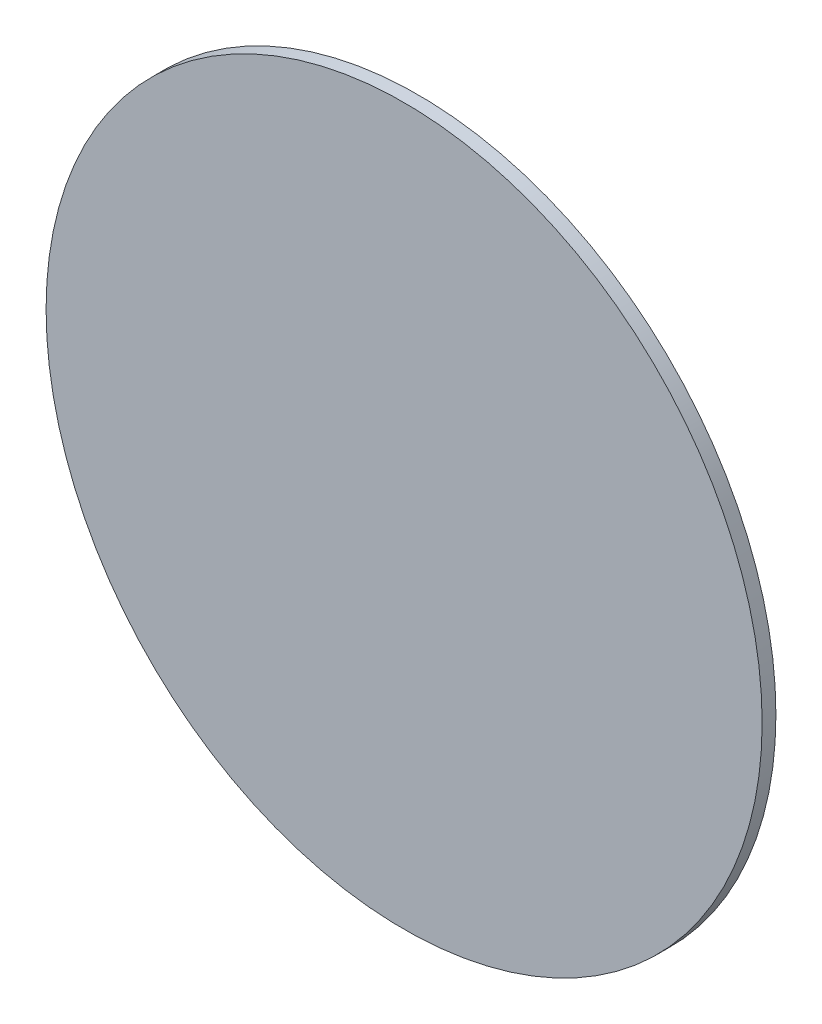
SolidWorks part; units mm, degrees
material "6061 Alloy"
ref_plane "Front Plane" through (0, 0, 0) normal (0, 0, 1) x (1, 0, 0)
ref_plane "Top Plane" through (0, 0, 0) normal (0, 1, 0) x (1, 0, 0)
ref_plane "Right Plane" through (0, 0, 0) normal (1, 0, 0) x (0, 0, -1)
sketch "Sketch1" plane through (0, 0, 0) normal (0, 0, 1) x (1, 0, 0)
  line L0 (6.5991, -21.59) -> (27.0559, -57.0222) construction
  line L1 (20.4568, -68.4522) -> (-20.4568, -68.4522) construction
  line L2 (-27.0559, -57.0222) -> (-6.5991, -21.59) construction
  line L3 (-15.3979, -16.51) -> (-35.8547, -51.9422) construction
  line L4 (-49.0529, -51.9422) -> (-69.5097, -16.51) construction
  line L5 (-62.9106, -5.08) -> (-21.997, -5.08) construction
  line L6 (-21.997, 5.08) -> (-62.9106, 5.08) construction
  line L7 (-69.5097, 16.51) -> (-49.0529, 51.9422) construction
  line L8 (-35.8547, 51.9422) -> (-15.3979, 16.51) construction
  line L9 (-6.5991, 21.59) -> (-27.0559, 57.0222) construction
  line L10 (-20.4568, 68.4522) -> (20.4568, 68.4522) construction
  line L11 (27.0559, 57.0222) -> (6.5991, 21.59) construction
  line L12 (15.3979, 16.51) -> (35.8547, 51.9422) construction
  line L13 (49.0529, 51.9422) -> (69.5097, 16.51) construction
  line L14 (62.9106, 5.08) -> (21.997, 5.08) construction
  line L15 (21.997, -5.08) -> (62.9106, -5.08) construction
  line L16 (69.5097, -16.51) -> (49.0529, -51.9422) construction
  line L17 (35.8547, -51.9422) -> (15.3979, -16.51) construction
  circle A0 centre (0, 114.3) radius 34.8615 construction
  circle A1 centre (98.9867, 57.15) radius 34.8615 construction
  circle A2 centre (98.9867, -57.15) radius 34.8615 construction
  circle A3 centre (0, -114.3) radius 34.8615 construction
  circle A4 centre (-98.9867, -57.15) radius 34.8615 construction
  circle A5 centre (-98.9867, 57.15) radius 34.8615 construction
  circle A6 centre (0, 0) radius 165.1
  circle A7 centre (0, 0) radius 12.7 construction
  arc A8 (-20.4568, -68.4522) -> (-27.0559, -57.0222) centre (-20.4568, -60.8322) cw construction
  arc A9 (27.0559, -57.0222) -> (20.4568, -68.4522) centre (20.4568, -60.8322) cw construction
  arc A10 (6.5991, -21.59) -> (-6.5991, -21.59) centre (0, -25.4) ccw construction
  arc A11 (-69.5097, -16.51) -> (-62.9106, -5.08) centre (-62.9106, -12.7) cw construction
  arc A12 (-35.8547, -51.9422) -> (-49.0529, -51.9422) centre (-42.4538, -48.1322) cw construction
  arc A13 (-15.3979, -16.51) -> (-21.997, -5.08) centre (-21.997, -12.7) ccw construction
  arc A14 (-49.0529, 51.9422) -> (-35.8547, 51.9422) centre (-42.4538, 48.1322) cw construction
  arc A15 (-62.9106, 5.08) -> (-69.5097, 16.51) centre (-62.9106, 12.7) cw construction
  arc A16 (-21.997, 5.08) -> (-15.3979, 16.51) centre (-21.997, 12.7) ccw construction
  arc A17 (20.4568, 68.4522) -> (27.0559, 57.0222) centre (20.4568, 60.8322) cw construction
  arc A18 (-27.0559, 57.0222) -> (-20.4568, 68.4522) centre (-20.4568, 60.8322) cw construction
  arc A19 (-6.5991, 21.59) -> (6.5991, 21.59) centre (0, 25.4) ccw construction
  arc A20 (69.5097, 16.51) -> (62.9106, 5.08) centre (62.9106, 12.7) cw construction
  arc A21 (35.8547, 51.9422) -> (49.0529, 51.9422) centre (42.4538, 48.1322) cw construction
  arc A22 (15.3979, 16.51) -> (21.997, 5.08) centre (21.997, 12.7) ccw construction
  arc A23 (49.0529, -51.9422) -> (35.8547, -51.9422) centre (42.4538, -48.1322) cw construction
  arc A24 (62.9106, -5.08) -> (69.5097, -16.51) centre (62.9106, -12.7) cw construction
  arc A25 (21.997, -5.08) -> (15.3979, -16.51) centre (21.997, -12.7) ccw construction
  point P16 (0, 0)
  point P22 (-33.655, -68.4522)
  point P27 (0, -10.16)
  point P76 (0, 0)
  dimension "D1" = 69.723
  dimension "D4" = 330.2
  dimension "D5" = 25.4
  dimension "D6" = 67.31
  dimension "D7" = 7.62
  dimension "D10" = 114.3
  dimension "D2" = 114.3
  dimension "D8" = 25.4
  dimension "D3" = 6
  dimension "D9" = 6
extrude "Boss-Extrude1" add sketch "Sketch1" along normal mid plane 6.35
sketch "Sketch2" plane through (0, 0, -3.175) normal (0, 0, -1) x (-1, 0, 0)
  line L1 (-21.997, 5.08) -> (-62.9106, 5.08) construction
  circle A0 centre (-23.8125, 0) radius 2.5908 construction
  circle A2 centre (-11.9062, 20.6222) radius 2.5908 construction
  circle A3 centre (11.9063, 20.6222) radius 2.5908 construction
  circle A4 centre (23.8125, 0) radius 2.5908 construction
  circle A5 centre (11.9062, -20.6222) radius 2.5908 construction
  circle A6 centre (-11.9063, -20.6222) radius 2.5908 construction
  circle A8 centre (0, 0) radius 12.7 construction
  point P16 (0, 0)
  dimension "D1" = 5.1816
  dimension "D2" = 47.625
  dimension "D4" = 23.8125
  dimension "D5" = 5.08
  dimension "D3" = 6
extrude "Cut-Extrude1" cut sketch "Sketch2" against normal up to surface (6.35 mm away) rebuild error yes up to face at (165.1, 0, 3.175)
